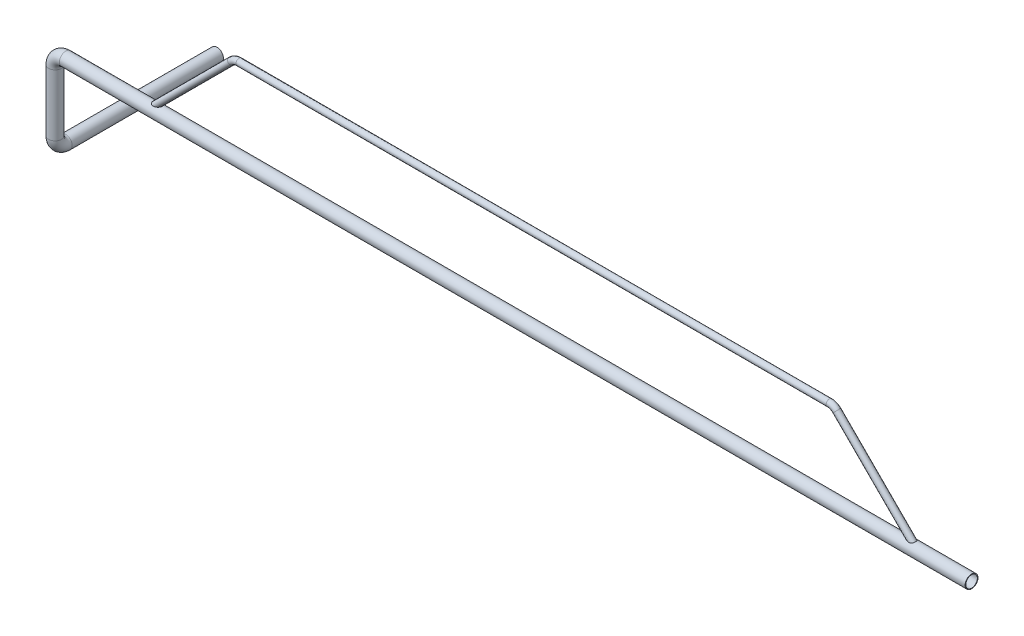
SolidWorks part; units mm, degrees
ref_plane "Plano frontal" through (0, 0, 0) normal (0, 0, 1) x (1, 0, 0)
ref_plane "Plano superior" through (0, 0, 0) normal (0, 1, 0) x (1, 0, 0)
ref_plane "Plano direito" through (0, 0, 0) normal (1, 0, 0) x (0, 0, -1)
sketch3d "3DSketch1"
  line L0 (-24893.1576, -8333.5147, 39491.7002) -> (-29116.6576, -8333.5147, 39491.7002)
  line L2 (-29166.6576, -8383.5147, 39491.7002) -> (-29166.6576, -8670.2286, 39491.7002)
  line L3 (-29166.6576, -8720.2286, 39441.7002) -> (-29166.6576, -8720.2286, 38736.7002)
  line L4 (-29166.6576, -8720.2286, 38736.7002) -> (-29166.6576, -8720.2286, 38707.7002) construction
  arc A0 (-29166.6576, -8670.2286, 39491.7002) -> (-29166.6576, -8720.2286, 39441.7002) centre (-29166.6576, -8670.2286, 39441.7002) ccw
  arc A1 (-29166.6576, -8383.5147, 39491.7002) -> (-29116.6576, -8333.5147, 39491.7002) centre (-29116.6576, -8383.5147, 39491.7002) ccw
  point P11 (-29166.6576, -8720.2286, 39491.7002)
  point P12 (-29116.6576, -8670.2286, 39441.7002)
  point P15 (-29166.6576, -8333.5147, 39491.7002)
  point P16 (-29116.6576, -8383.5147, 39441.7002)
  dimension "D1" = 50
sweep "Sweep-Thin1" add path "3DSketch1" circular profile diameter 60 parameters "D1"=3, "D3"=60
sketch3d "3DSketch2"
  line L0 (-25145.0863, -8333.5147, 39491.7002) -> (-25521.0143, -7957.5868, 39491.7002)
  line L1 (-24893.1576, -8333.5147, 39491.7002) -> (-29116.6576, -8333.5147, 39491.7002) construction
  line L2 (-25556.3696, -7942.9421, 39491.7002) -> (-28308.5343, -7942.9421, 39491.7002)
  line L3 (-28343.8896, -7957.5868, 39491.7002) -> (-28719.8175, -8333.5147, 39491.7002)
  line L5 (-25564.6775, -7942.9421, 39491.7002) -> (-25564.6775, -8333.5147, 39491.7002) construction
  arc A0 (-28308.5343, -7942.9421, 39491.7002) -> (-28343.8896, -7957.5868, 39491.7002) centre (-28308.5343, -7992.9421, 39491.7002) ccw
  arc A1 (-25521.0143, -7957.5868, 39491.7002) -> (-25556.3696, -7942.9421, 39491.7002) centre (-25556.3696, -7992.9421, 39491.7002) ccw
  point P24 (-28329.2449, -7942.9421, 39491.7002)
  point P26 (-28308.5343, -7992.9421, 39541.7002)
  point P29 (-25535.6589, -7942.9421, 39491.7002)
  point P30 (-25556.3696, -7992.9421, 39541.7002)
  dimension "D3" = 50
  dimension "D1" = 135
  dimension "D2" = 135
sweep "Sweep-Thin2" add path "3DSketch2" circular profile diameter 30 parameters "D1"=3, "D3"=30
